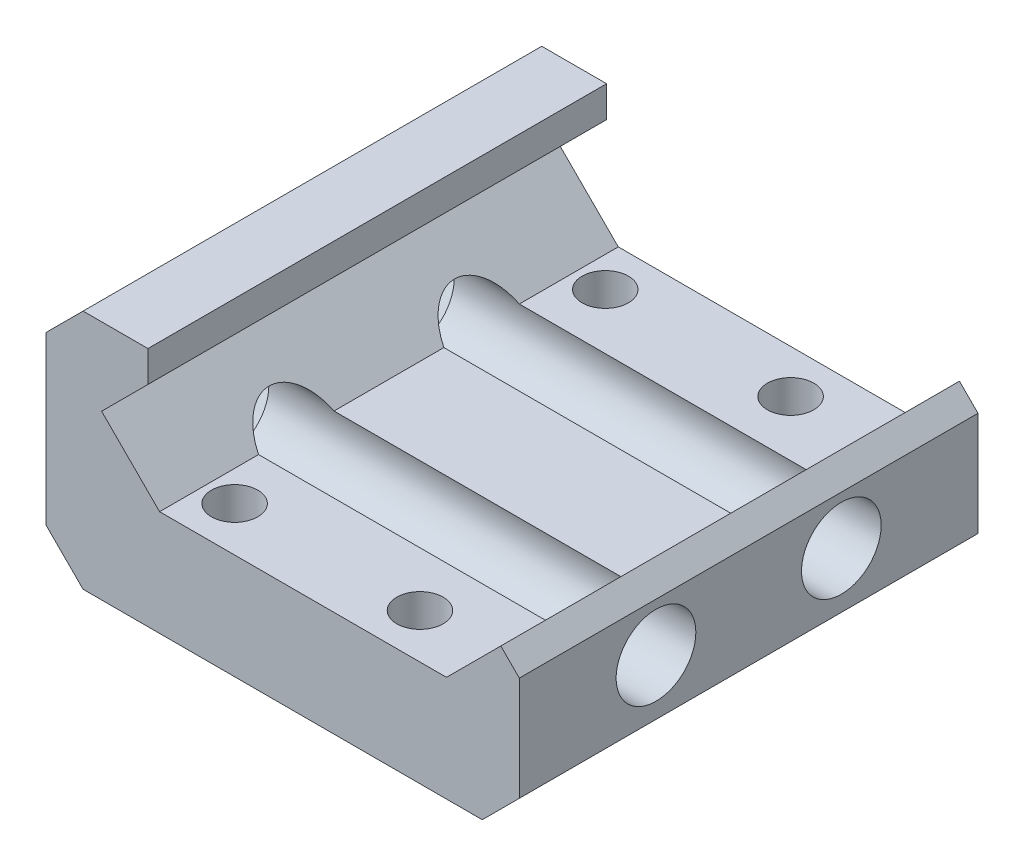
SolidWorks part; units mm, degrees
ref_plane "Płaszczyzna przednia" through (0, 0, 0) normal (0, 0, 1) x (1, 0, 0)
ref_plane "Płaszczyzna górna" through (0, 0, 0) normal (0, 1, 0) x (1, 0, 0)
ref_plane "Płaszczyzna prawa" through (0, 0, 0) normal (1, 0, 0) x (0, 0, -1)
sketch "Szkic1" plane through (0, 0, 0) normal (0, 0, 1) x (1, 0, 0)
  line L0 (-3, 4.18) -> (2.5, 4.18)
  line L2 (-3, -8.82) -> (-3, 4.18)
  line L5 (22.74, -1) -> (22.74, -7.02) construction
  line L6 (1.37, -1.37) -> (20.37, -1.37) construction
  line L7 (2.5, 4.18) -> (2.5, 2.5)
  line L8 (2.5, 2.5) -> (0, 0)
  line L9 (0, 0) -> (3.13, -3.13)
  line L10 (3.13, -3.13) -> (18.61, -3.13)
  line L11 (18.61, -3.13) -> (22.54, 0.8)
  line L14 (22.54, 0.8) -> (22.54, -6.82)
  line L17 (22.54, -6.82) -> (20.54, -8.82)
  line L18 (-3, -8.82) -> (20.54, -8.82)
  line L19 (1.37, -1.37) -> (1.37, 1.37) construction
  line L20 (1.37, 1.37) -> (20.37, 1.37) construction
  line L21 (20.37, -1.37) -> (20.37, 1.37) construction
  dimension "D1" = 45
  dimension "D2" = 45
  dimension "D3" = 5.5
  dimension "D4" = 1.68
  dimension "D5" = 13
  dimension "D6" = 2
  dimension "D7" = 19
  dimension "D8" = 2.74
  dimension "D9" = 4.5
  dimension "D10" = 3
  dimension "D11" = 0.2
extrude "Dodanie-wyciągnięcie3" add sketch "Szkic1" along normal blind 24.75
sketch "Szkic3" plane through (22.54, 0, 0) normal (1, 0, 0) x (0, 0, -1)
  line L1 (-7.375, -3.82) -> (-17.375, -3.82) construction
  line L3 (-24.75, -6.82) -> (0, -6.82) construction
  line L4 (-24.75, -6.82) -> (0, -6.82) construction
  line L5 (-12.375, -6.82) -> (-12.375, -3.82) construction
  circle A0 centre (-17.375, -3.82) radius 2.15
  circle A1 centre (-7.375, -3.82) radius 2.15
  dimension "D1" = 10
  dimension "D2" = 4.3
  dimension "D3" = 5
extrude "Wytnij-wyciągnięcie1" cut sketch "Szkic3" against normal through all
sketch "Szkic4" plane through (0, -3.13, 0) normal (0, 1, 0) x (1, 0, 0)
  line L0 (18.61, -24.75) -> (3.13, -24.75) construction
  circle A0 centre (0, -2.75) radius 2
  circle A1 centre (0, -22) radius 2
  dimension "D2" = 2.75
  dimension "D3" = 2.75
extrude "Wytnij-wyciągnięcie2" [suppressed] cut sketch "Szkic4" against normal blind 6
sketch "Szkic7" [suppressed] plane through (0, -3.13, 0) normal (0, 1, 0) x (1, 0, 0)
  circle A0 centre (0, -2.75) radius 2.5
  circle A1 centre (0, -22) radius 2.5
  dimension "D1" = 2.75
  dimension "D2" = 19.25
extrude "Wytnij-wyciągnięcie3" [suppressed] cut sketch "Szkic7" against normal blind 1.5
sketch "Sketch1" plane through (0, 0, 24.75) normal (0, 0, 1) x (1, 0, 0)
  line L2 (22.54, -6.82) -> (22.54, 0.8) construction
  line L3 (22.54, -1.2) -> (21.54, -0.2)
  line L13 (-3, -8.82) -> (20.54, -8.82)
  line L14 (20.54, -8.82) -> (22.54, -6.82)
  line L15 (22.54, -6.82) -> (22.54, 0.8)
  line L16 (22.54, 0.8) -> (18.61, -3.13)
  line L17 (18.61, -3.13) -> (3.13, -3.13)
  line L18 (3.13, -3.13) -> (0, 0)
  line L19 (0, 0) -> (2.5, 2.5)
  line L20 (2.5, 2.5) -> (2.5, 4.18)
  line L21 (2.5, 4.18) -> (-3, 4.18)
  line L22 (-3, 4.18) -> (-3, -8.82)
  line L25 (22.54, -1.2) -> (22.54, 0.8)
  line L26 (22.54, 0.8) -> (21.54, -0.2)
  dimension "D1" = 2
  dimension "D2" = 0
extrude "Cut-Extrude1" cut sketch "Sketch1" against normal through all
sketch "Sketch3" plane through (22.54, 0, 0) normal (1, 0, 0) x (0, 0, -1)
  circle A0 centre (-17.375, -3.82) radius 2.65
  circle A1 centre (-7.375, -3.82) radius 2.65
  dimension "D1" = 5.3
chamfer "Chamfer1" distance 2 angle 45 2 edges at (-3, 4.18, 12.375) (-3, -8.82, 12.375)
hole_wizard "Ø2.5 (2.5) Diameter Hole1" positions "Sketch4" profile "Sketch5" hole size "Ø2.5" standard "DIN" end condition through all
sketch "Sketch4" plane through (0, -8.82, 0) normal (0, -1, 0) x (-1, 0, 0)
  line L0 (-9.77, -19.9336) -> (-9.77, -24.75) construction
  line L4 (-4.77, -22.3418) -> (-9.77, -22.3418) construction
  line L6 (-9.77, 0) -> (-9.77, -4.8164) construction
  line L10 (-9.32, -2.3418) -> (-4.77, -2.3418) construction
  line L14 (1, -24.75) -> (-20.54, -24.75) construction
  point P0 (-4.77, -2.3418)
  point P4 (-14.77, -2.3418)
  point P5 (-14.77, -22.3418)
  point P6 (-4.77, -22.3418)
  dimension "D3" = 10
  dimension "D4" = 20
  dimension "D5" = 5
  dimension "D1" = 2
  dimension "D2" = 2
sketch "Sketch5" plane through (4.77, -8.82, 2.3418) normal (1, 0, 0) x (0, 0, -1)
  line L0 (0, 0) -> (0, 13)
  line L1 (0, 13) -> (1.25, 13)
  line L2 (1.25, 13) -> (1.25, 0)
  line L5 (1.25, 0) -> (0, 0)
  line L11 (0, -6.35) -> (0, 107.95) construction
  dimension "Thru Hole Dia." = 2.5
  dimension "Thru Hole Depth" = 13
sketch "Sketch6" plane through (-3, 0, 0) normal (-1, 0, 0) x (0, 0, 1)
  line L1 (9.3669, -7.27) -> (11.3587, -3.82)
  line L2 (11.3587, -3.82) -> (9.3669, -0.37)
  line L3 (9.3669, -0.37) -> (5.3831, -0.37)
  line L4 (5.3831, -0.37) -> (3.3913, -3.82)
  line L5 (3.3913, -3.82) -> (5.3831, -7.27)
  line L6 (5.3831, -7.27) -> (9.3669, -7.27)
  line L7 (15.3831, -7.27) -> (19.3669, -7.27)
  line L8 (19.3669, -7.27) -> (21.3587, -3.82)
  line L9 (21.3587, -3.82) -> (19.3669, -0.37)
  line L10 (19.3669, -0.37) -> (15.3831, -0.37)
  line L11 (15.3831, -0.37) -> (13.3913, -3.82)
  line L12 (13.3913, -3.82) -> (15.3831, -7.27)
  circle A0 centre (7.375, -3.82) radius 3.45 construction
  circle A1 centre (17.375, -3.82) radius 3.45 construction
  point P10 (7.375, -3.82)
  dimension "D1" = 6.9
extrude "Cut-Extrude2" cut sketch "Sketch6" against normal blind 2.5
